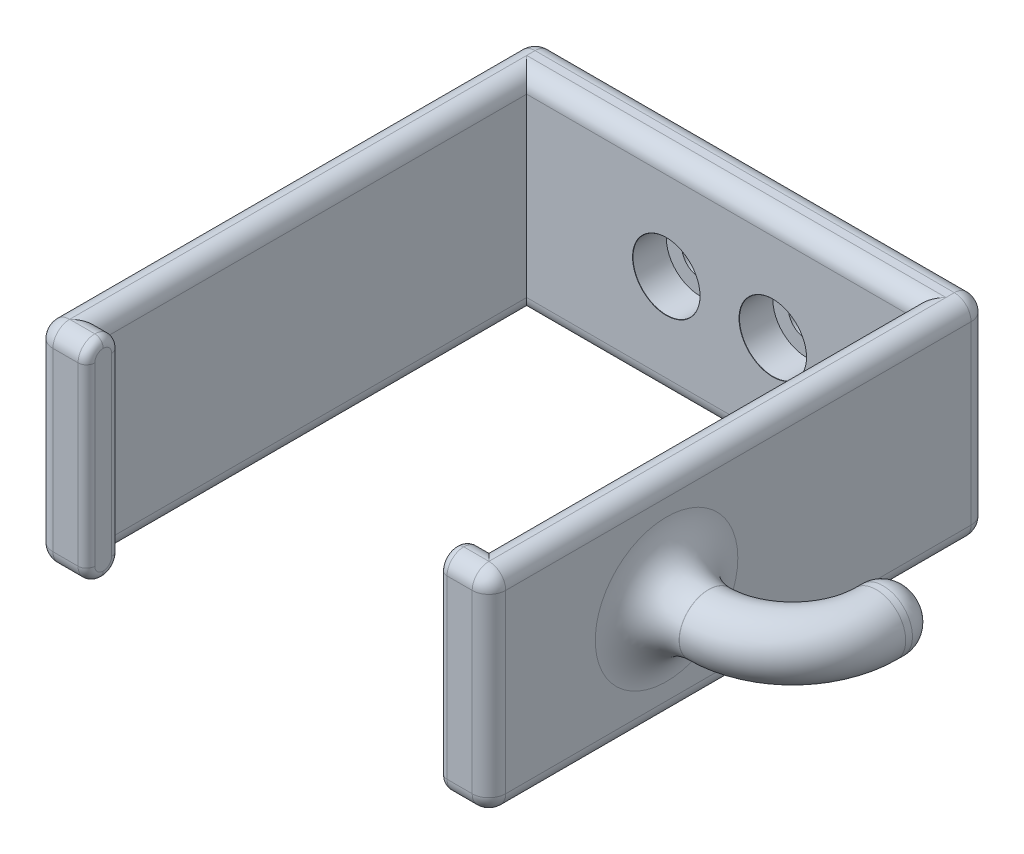
SolidWorks part; units mm, degrees
ref_plane "Front Plane" through (0, 0, 0) normal (0, 0, 1) x (1, 0, 0)
ref_plane "Top Plane" through (0, 0, 0) normal (0, 1, 0) x (1, 0, 0)
ref_plane "Right Plane" through (0, 0, 0) normal (1, 0, 0) x (0, 0, -1)
sketch "Sketch1" plane through (0, 0, 0) normal (0, 1, 0) x (1, 0, 0)
  line L0 (18, -1.7245) -> (18, -52.2245)
  line L1 (-32, 3.2755) -> (22, 3.2755)
  line L2 (-32, 3.2755) -> (-32, -5)
  line L3 (-28, -1.7245) -> (18, -1.7245)
  line L4 (22, 3.2755) -> (22, -5)
  line L6 (-28, -56.2245) -> (-26, -56.2245)
  line L7 (-32, 3.2755) -> (-25, 3.2755)
  line L8 (-32, 3.2755) -> (-32, -56.2245)
  line L9 (-32, -56.2245) -> (-28, -56.2245)
  line L10 (-28, -1.7245) -> (-28, -52.2245)
  line L11 (22, 3.2755) -> (25, 3.2755)
  line L12 (22, 3.2755) -> (22, -56.2245)
  line L13 (22, -56.2245) -> (18, -56.2245)
  line L16 (-28, -52.2245) -> (-26, -52.2245)
  line L17 (-26, -56.2245) -> (-26, -52.2245)
  line L18 (18, -56.2245) -> (16, -56.2245)
  line L20 (18, -52.2245) -> (16, -52.2245)
  line L21 (16, -56.2245) -> (16, -52.2245)
  point P0 (0, 0)
  dimension "D1" = 2
  dimension "D2" = 4
  dimension "D3" = 4
  dimension "D4" = 5
  dimension "D5" = 2
  dimension "D6" = 50.5
  dimension "D7" = 4
  dimension "D8" = 46
extrude "Boss-Extrude1" add sketch "Sketch1" along normal blind 25 contours L13 L12 L4 L1 L2 L8 L9 L10 L3 L0 region at (-5, 0, 0.921)
fillet "Fillet1" radius 1 8 edges at (16, 12.5, 52.2245) (16, 25, 54.2245) (16, 12.5, 56.2245) (16, 0, 54.2245) (-26, 12.5, 56.2245) (-26, 25, 54.2245) (-26, 12.5, 52.2245) (-26, 0, 54.2245)
sketch "Sketch2" plane through (0, 0, 1.7245) normal (0, 0, 1) x (1, 0, 0)
  line L0 (-5, 0) -> (-5, 25) construction
  line L1 (-28, 25) -> (18, 25) construction
  line L3 (-28, 0) -> (18, 0) construction
  line L4 (18, 12.5) -> (-28, 12.5) construction
  line L5 (18, 25) -> (18, 0) construction
  line L6 (-28, 25) -> (-28, 0) construction
  circle A0 centre (1.35, 12.5) radius 2
  circle A1 centre (-11.35, 12.5) radius 2
  dimension "D3" = 4
  dimension "D4" = 4
  dimension "D1" = 12.7
  dimension "D2" = 6.35
hole_wizard "CBORE for M4 SHCS1" positions "3DSketch1" profile "Sketch3" counterbore size "M4" standard "ANSI Metric" end condition through all
sketch3d "3DSketch1"
  point P0 (1.35, 12.5, 1.7245)
  point P3 (-11.35, 12.5, 1.7245)
sketch "Sketch3" plane through (1.35, 12.5, 1.7245) normal (1, 0, 0) x (0, -1, 0)
  line L0 (0, 0) -> (0, 5)
  line L1 (0, 5) -> (2.15, 5)
  line L3 (2.15, 5) -> (2.15, 4)
  line L4 (4, 4) -> (2.15, 4)
  line L5 (4, 4) -> (4, 0.025)
  line L6 (4, 0.025) -> (4.025, 0)
  line L7 (4.025, 0) -> (0, 0)
  line L8 (-4, 0.025) -> (-4.025, 0) construction
  line L11 (0, -6.35) -> (0, 107.95) construction
  dimension "Thru Hole Dia." = 4.3
  dimension "Thru Hole Depth" = 5
  dimension "C'Bore Dia." = 8
  dimension "C'Bore Depth" = 4
  dimension "Near C'Sink Dia." = 8.05
  dimension "Near C'Sink Angle" = 90
fillet "Fillet2" radius 2 32 edges at (16.2929, 24.7071, 52.5174) (16.2929, 24.7071, 55.9316) (-26.2929, 24.7071, 55.9316) (-26.2929, 24.7071, 52.5174) (16.2929, 0.2929, 55.9316) (16.2929, 0.2929, 52.5174) (-26.2929, 0.2929, 52.5174) (-26.2929, 0.2929, 55.9316) (-5, 0, -3.2755) (-29.5, 0, 56.2245) (-27.5, 0, 52.2245) (-28, 0, 26.9745) (-5, 0, 1.7245) (18, 0, 26.9745) (17.5, 0, 52.2245) (19.5, 0, 56.2245) (18, 25, 26.9745) (-5, 25, 1.7245) (-28, 25, 26.9745) (-27.5, 25, 52.2245) (-29.5, 25, 56.2245) (-5, 25, -3.2755) (19.5, 25, 56.2245) (17.5, 25, 52.2245) (-32, 12.5, -3.2755) (-32, 25, 26.4745) (-32, 12.5, 56.2245) (-32, 0, 26.4745) (22, 12.5, 56.2245) (22, 25, 26.4745) (22, 12.5, -3.2755) (22, 0, 26.4745)
sketch "Sketch4" plane through (22, 0, 0) normal (1, 0, 0) x (0, 0, -1)
  line L0 (-54.2245, 23) -> (-54.2245, 2) construction
  circle A0 centre (-35.0428, 12.5) radius 3.5
  point P4 (-54.2245, 12.5)
  dimension "D1" = 7
ref_plane "Plane1" through (0, 12.5, 0) normal (0, 1, 0) x (1, 0, 0)
sketch "Sketch6" plane through (0, 12.5, 0) normal (0, 1, 0) x (1, 0, 0)
  line L0 (22, -35.0428) -> (27.02, -35.0428)
  line L1 (37.02, -25.0428) -> (37.02, -21.237)
  arc A0 (27.02, -35.0428) -> (37.02, -25.0428) centre (27.02, -25.0428) ccw
  dimension "D1" = 10
sweep "Sweep2" add profiles "Sketch4" path "Sketch6"
fillet "Fillet3" radius 5 1 edges at (22, 12.5, 31.5428)
fillet "Fillet4" radius 3 1 edges at (33.52, 12.5, 21.237)
equation "\"D2@Sketch2\"=\"D1@Sketch2\"/2"
